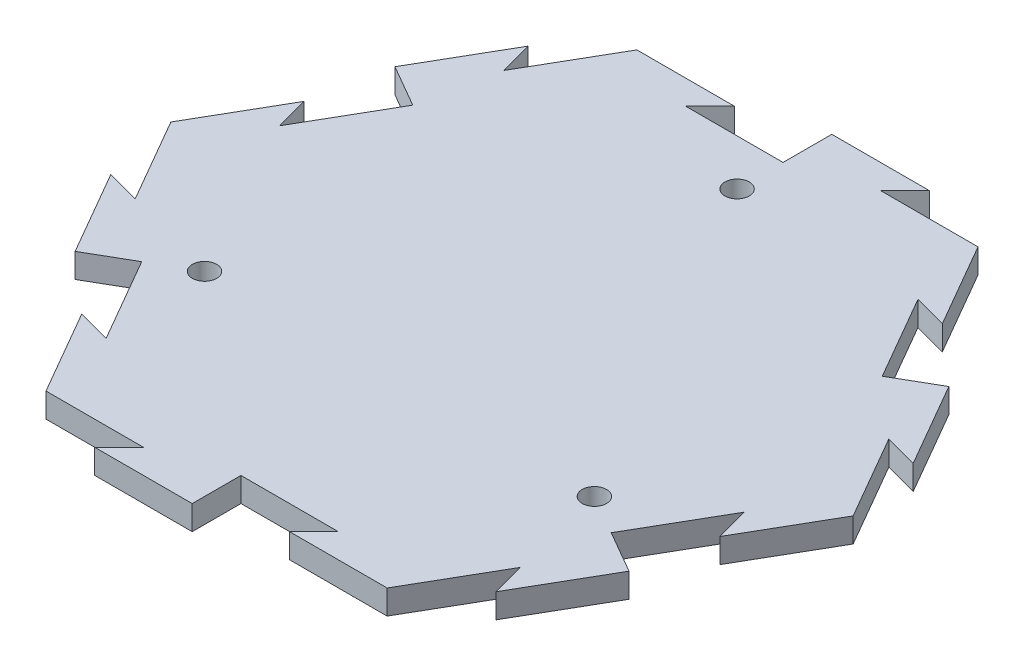
SolidWorks part; units mm, degrees
material "Cedar"
ref_plane "Front Plane" through (0, 0, 0) normal (0, 0, 1) x (1, 0, 0)
ref_plane "Top Plane" through (0, 0, 0) normal (0, 1, 0) x (1, 0, 0)
ref_plane "Right Plane" through (0, 0, 0) normal (1, 0, 0) x (0, 0, -1)
sketch "Sketch1" plane through (0, 0, 0) normal (0, 1, 0) x (1, 0, 0)
  line L0 (0, 0) -> (88.9, 0) construction
  line L1 (88.9, 0) -> (44.45, 76.9897)
  line L2 (44.45, 76.9897) -> (-44.45, 76.9897)
  line L3 (-44.45, 76.9897) -> (-88.9, 0)
  line L4 (-88.9, 0) -> (-44.45, -76.9897)
  line L5 (-44.45, -76.9897) -> (44.45, -76.9897)
  line L6 (44.45, -76.9897) -> (88.9, 0)
  circle A0 centre (0, 0) radius 76.9897 construction
  dimension "D1" = 88.9
extrude "Boss-Extrude1" add sketch "Sketch1" against normal blind 6.35
sketch "Sketch2" plane through (0, 0, 0) normal (0, 1, 0) x (1, 0, 0)
  point P1 (0, 0)
ref_axis "Axis1" through (0, 0, 0) along (0, 1, 0)
sketch "Sketch9" plane through (0, 0, 0) normal (0, 1, 0) x (1, 0, 0)
  line L1 (50.8, -29.3294) -> (0, 58.6588) construction
  line L2 (0, 58.6588) -> (-50.8, -29.3294) construction
  line L3 (-50.8, -29.3294) -> (50.8, -29.3294) construction
  circle A0 centre (0, 0) radius 29.3294 construction
  circle A1 centre (-50.8, -29.3294) radius 3.175
  dimension "D2" = 6.35
  dimension "D1" = 101.6
extrude "Cut-Extrude3" cut sketch "Sketch9" against normal through all
pattern_circular "CirPattern6" count 3 over 360 about axis through (0, 0, 0) along (0, 1, 0) of "Cut-Extrude3"
sketch "Sketch10" plane through (0, 0, 0) normal (0, 1, 0) x (1, 0, 0)
  line L0 (44.45, 76.9897) -> (57.15, 54.9926) construction
  line L1 (57.15, 54.9926) -> (48.4757, 57.3169)
  line L2 (48.4757, 57.3169) -> (61.1757, 35.3198)
  line L3 (61.1757, 35.3198) -> (66.675, 38.4948)
  line L4 (57.15, 54.9926) -> (66.675, 38.4948)
  line L5 (88.9, 0) -> (44.45, 76.9897) construction
  dimension "D1" = 45
  dimension "D2" = 6.35
extrude "Cut-Extrude4" cut sketch "Sketch10" against normal through all
sketch "Sketch11" plane through (0, 0, 0) normal (0, 1, 0) x (1, 0, 0)
  line L0 (66.675, 38.4948) -> (88.9, 0) construction
  line L1 (66.675, 38.4948) -> (72.1743, 41.6698)
  line L2 (72.1743, 41.6698) -> (84.8743, 19.6728)
  line L3 (84.8743, 19.6728) -> (76.2, 21.997)
  line L4 (76.2, 21.997) -> (66.675, 38.4948)
  line L5 (76.2, 21.997) -> (88.9, 0) construction
  line L6 (76.2, 21.997) -> (88.9, 0) construction
  line L7 (88.9, 0) -> (66.675, 38.4948) construction
  line L8 (44.45, -76.9897) -> (88.9, 0) construction
  dimension "D1" = 45
  dimension "D2" = 6.35
extrude "Boss-Extrude4" add sketch "Sketch11" against normal blind 6.35
pattern_circular "CirPattern7" count 6 over 360 about axis through (0, 0, 0) along (0, 1, 0) of "Cut-Extrude4", "Boss-Extrude4"
